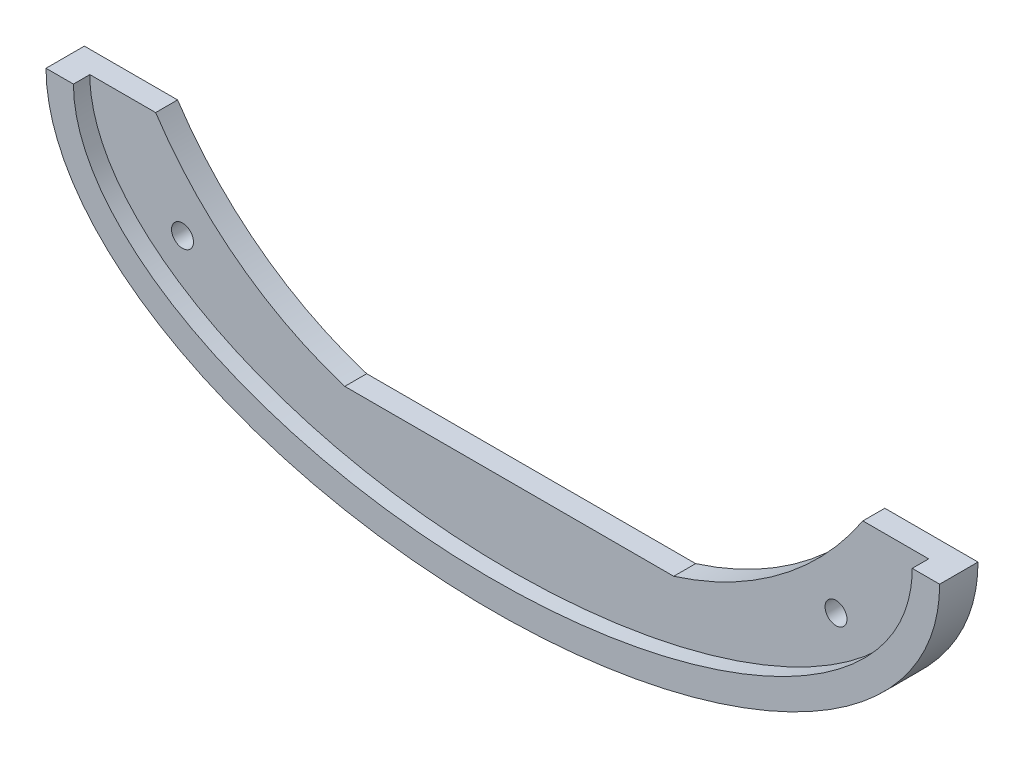
SolidWorks part; units mm, degrees
ref_plane "Alzado" through (0, 0, 0) normal (0, 0, 1) x (1, 0, 0)
ref_plane "Planta" through (0, 0, 0) normal (0, 1, 0) x (1, 0, 0)
ref_plane "Vista lateral" through (0, 0, 0) normal (1, 0, 0) x (0, 0, -1)
sketch "Croquis1" plane through (0, 0, 0) normal (0, 0, 1) x (1, 0, 0)
  line L0 (0, 14) -> (30, 14)
  line L3 (-76.5, 40) -> (-64.5, 40)
  line L5 (0, 14) -> (-30, 14)
  line L6 (0, 0) -> (0, 40) construction
  line L7 (64.5, 40) -> (76.5, 40)
  line L8 (-59.6, 23) -> (59.6, 23) construction
  circle A0 centre (7.25, 8) radius 2
  circle A1 centre (59.6, 23) radius 2
  circle A2 centre (-7.25, 8) radius 2
  circle A3 centre (-59.6, 23) radius 2
  arc A6 (-30, 14) -> (-64.5, 40) centre (-10.6545, 75.5595) cw
  arc A7 (30, 14) -> (64.5, 40) centre (10.6545, 75.5595) ccw
  ellipse E0 centre (0, 40) end of major axis (76.5, 40) minor radius 40 (-76.5, 40) -> (76.5, 40) ccw
  dimension "D3" = 4
  dimension "D5" = 4
  dimension "D10" = 8
  dimension "D2" = 153
  dimension "D4" = 30
  dimension "D6" = 119.2
  dimension "D7" = 15
  dimension "D8" = 40
  dimension "D9" = 12
  dimension "D11" = 14.5
  dimension "D12" = 14
extrude "Saliente-Extruir1" add sketch "Croquis1" along normal blind 4
ref_plane "Plano1" through (0, 0, -3) normal (0, 0, -1) x (-1, 0, 0)
sketch "Croquis2" plane through (0, 0, -3) normal (0, 0, -1) x (-1, 0, 0)
  line L3 (0, 0) -> (0, 33.4572) construction
  line L6 (64.5, 40) -> (76.5, 40) construction
  line L7 (-30, 14) -> (30, 14) construction
  line L8 (-76.5, 40) -> (-64.5, 40) construction
  line L9 (64.5, 40) -> (76.5, 40)
  line L10 (-30, 14) -> (30, 14)
  line L11 (-76.5, 40) -> (-64.5, 40)
  arc A8 (30, 14) -> (64.5, 40) centre (10.6545, 75.5595) ccw construction
  circle A10 centre (-59.6, 23) radius 2 construction
  circle A12 centre (7.25, 8) radius 2 construction
  circle A13 centre (-7.25, 8) radius 2 construction
  arc A14 (-64.5, 40) -> (-30, 14) centre (-10.6545, 75.5595) ccw construction
  arc A15 (30, 14) -> (64.5, 40) centre (10.6545, 75.5595) ccw
  circle A17 centre (-59.6, 23) radius 2
  circle A19 centre (7.25, 8) radius 2
  circle A20 centre (-7.25, 8) radius 2
  arc A21 (-64.5, 40) -> (-30, 14) centre (-10.6545, 75.5595) ccw
  circle A22 centre (59.6, 23) radius 2 construction
  circle A23 centre (59.6, 23) radius 2
  ellipse E0 centre (0, 40) end of major axis (-76.5, 40) minor radius 40 (-76.5, 40) -> (76.5, 40) ccw construction
  ellipse E1 centre (0, 40) end of major axis (-76.5, 40) minor radius 40 (-76.5, 40) -> (76.5, 40) ccw
extrude "Saliente-Extruir2" add sketch "Croquis2" along normal blind 4 separate body
ref_plane "Plano2" through (0, 0, 4) normal (0, 0, 1) x (1, 0, 0)
sketch "Croquis3" plane through (0, 0, 4) normal (0, 0, 1) x (1, 0, 0)
  line L2 (-81.5, 40) -> (-76.5, 40)
  line L3 (81.5, 40) -> (76.5, 40)
  ellipse E1 centre (0, 40) end of major axis (76.5, 40) minor radius 40 (-76.5, 40) -> (76.5, 40) ccw construction
  ellipse E2 centre (0, 40) end of major axis (76.5, 40) minor radius 40 (-76.5, 40) -> (76.5, 40) ccw
  spline S0 degree 1 poles (-81.5, 40) (81.5, 40) knots 0 0 1 1 construction
  spline S1 degree 3 poles (-81.5, 40) (-81.5, 36.7505) (-80.261, 30.281) (-73.3217, 18.4428) (-57.7398, 6.4288) (-31.0655, -2.8514) (0, -6.0743) (31.0655, -2.8514) (57.7398, 6.4288) (73.3217, 18.4428) (80.261, 30.281) (81.5, 36.7505) (81.5, 40) knots 3.141593 3.141593 3.141593 3.141593 3.337942 3.534292 3.926991 4.31969 4.712389 5.105088 5.497787 5.890486 6.086836 6.283185 6.283185 6.283185 6.283185
  dimension "D1" = 5
extrude "Saliente-Extruir3" add sketch "Croquis3" against normal up to surface (11 mm away) contours L3 E2 L2 S1 up to face at (5.25, 8, -7)
sketch "Croquis4" plane through (0, 0, 0) normal (0, 0, 1) x (1, 0, 0)
  line L0 (30, 14) -> (-30, 14) construction
  line L1 (30, 14) -> (-30, 14)
  line L2 (-39.8217, 18) -> (39.8217, 18)
  arc A0 (-64.5, 40) -> (-30, 14) centre (-10.6545, 75.5595) ccw construction
  arc A1 (30, 14) -> (64.5, 40) centre (10.6545, 75.5595) ccw construction
  arc A2 (-39.8217, 18) -> (-30, 14) centre (-10.6545, 75.5595) ccw
  arc A3 (30, 14) -> (39.8217, 18) centre (10.6545, 75.5595) ccw
  dimension "D1" = 4
extrude "Saliente-Extruir4" add sketch "Croquis4" along normal blind 4
sketch "Croquis5" plane through (0, 0, 4) normal (0, 0, 1) x (1, 0, 0)
  line L0 (39.8217, 18) -> (-39.8217, 18) construction
  line L1 (40.755, 18) -> (-40.755, 18)
  line L2 (40.755, 18) -> (40.755, 14)
  line L3 (40.755, 14) -> (-40.755, 14)
  line L4 (-40.755, 18) -> (-40.755, 14)
  point P6 (0, 14)
  dimension "D1" = 4
  dimension "D2" = 81.51
extrude "Saliente-Extruir5" add sketch "Croquis5" along normal blind 45 contours L2 L1 L4 L3
sketch "Croquis6" plane through (0, 14, 0) normal (0, -1, 0) x (-1, 0, 0)
  line L0 (13.075, -29) -> (-13.075, -29) construction
  line L1 (40.755, -4) -> (-40.755, -4) construction
  line L2 (0, -4) -> (0, -39) construction
  line L3 (35.826, -4) -> (35.826, -49) construction
  line L4 (-40.755, -4) -> (40.755, -4) construction
  line L5 (-40.755, -49) -> (40.755, -49) construction
  circle A0 centre (13.075, -29) radius 8.15
  circle A1 centre (-13.075, -29) radius 8.125
  circle A2 centre (35.826, -43.4034) radius 2.65
  circle A3 centre (35.826, -33.4034) radius 2.65
  circle A4 centre (-35.826, -33.4034) radius 2.65
  circle A5 centre (-35.826, -43.4034) radius 2.65
  point P18 (0, -29)
  dimension "D2" = 16.3
  dimension "D3" = 16.25
  dimension "D6" = 5.3
  dimension "D7" = 5.3
  dimension "D4" = 26.15
  dimension "D1" = 25
  dimension "D8" = 10
extrude "Cortar-Extruir1" cut sketch "Croquis6" against normal blind 25 contours A2 | A3 | A0 | A1 | A5 | A4
ref_plane "Plano4" through (0, -1, 0) normal (0, 1, 0) x (1, 0, 0)
sketch "Croquis7" plane through (0, -1, 0) normal (0, 1, 0) x (1, 0, 0)
  line L0 (0, -9.7855) -> (0, 13.9568) construction
  line L1 (-81.5, -4) -> (81.5, -4) construction
  line L2 (-55, -4) -> (-45, -4)
  line L3 (-55, -4) -> (-55, 7)
  line L4 (-55, 7) -> (-45, 7)
  line L5 (-45, -4) -> (-45, 7)
  line L6 (81.5, 7) -> (-81.5, 7) construction
  line L7 (55, 7) -> (45, 7)
  line L8 (55, -4) -> (55, 7)
  line L9 (55, -4) -> (45, -4)
  line L10 (45, -4) -> (45, 7)
  dimension "D1" = 10
  dimension "D2" = 55
extrude "Saliente-Extruir6" [suppressed] add sketch "Croquis7" along normal up to surface and the other way blind 6.08
sketch "Croquis16" [suppressed] plane through (0, -9.08, 0) normal (0, -1, 0) x (1, 0, 0)
  line L8 (-50, -6.5) -> (-50, 4.3) construction
  line L9 (-55, -1.1) -> (-45, -1.1) construction
  line L18 (50, 4.3) -> (50, -6.5) construction
  line L19 (45, -1.1) -> (55, -1.1) construction
  circle A0 centre (-50, -1.1) radius 4
  circle A1 centre (50, -1.1) radius 4
  dimension "D1" = 8
  dimension "D2" = 8
extrude "Cortar-Extruir6" [suppressed] cut sketch "Croquis16" against normal blind 16.3
sketch "Croquis17" plane through (0, 14, 0) normal (0, -1, 0) x (1, 0, 0)
  line L0 (-20.0239, 37.988) -> (-14.3005, 42.0182) construction
  line L1 (-20.5996, 38.8056) -> (-14.8763, 42.8359)
  line L2 (-19.4481, 37.1703) -> (-13.7248, 41.2006)
  line L3 (14.2242, 42.0182) -> (19.9475, 37.988) construction
  line L4 (14.7999, 42.8359) -> (20.5233, 38.8056)
  line L5 (13.6484, 41.2006) -> (19.3718, 37.1703)
  line L7 (-0.0382, 31.8728) -> (-0.0382, 6.8728) construction
  line L8 (-14.3005, 42.0182) -> (14.2242, 42.0182) construction
  line L9 (-20.0239, 37.988) -> (19.9475, 37.988) construction
  arc A0 (-20.5996, 38.8056) -> (-19.4481, 37.1703) centre (-20.0239, 37.988) ccw
  arc A1 (-13.7248, 41.2006) -> (-14.8763, 42.8359) centre (-14.3005, 42.0182) ccw
  arc A2 (14.7999, 42.8359) -> (13.6484, 41.2006) centre (14.2242, 42.0182) ccw
  arc A3 (19.3718, 37.1703) -> (20.5233, 38.8056) centre (19.9475, 37.988) ccw
  arc A4 (-20.8514, 31.4391) -> (-21.2225, 29.203) centre (-13.075, 29) ccw
  arc A6 (-10.8066, 17.5553) -> (11.1701, 17.5553) centre (0.1818, 45.4654) ccw
  arc A7 (-11.1729, 16.6248) -> (11.5364, 16.6248) centre (0.1818, 45.4654) ccw
  arc A8 (-10.8066, 17.5553) -> (-11.1729, 16.6248) centre (-10.9898, 17.09) ccw
  arc A9 (11.5364, 16.6248) -> (11.1701, 17.5553) centre (11.3533, 17.09) ccw
  circle A10 centre (-13.075, 29) radius 8.15 construction
  arc A13 (20.7751, 31.4391) -> (21.1461, 29.203) centre (12.9987, 29) cw
  ellipse E0 centre (-0.0382, 20.6274) end of major axis (3.8018, 20.6274) minor radius 1.3066
  spline S0 degree 2 poles (-20.8514, 31.4391) (-23.6077, 31.2523) (-25.4765, 33.8858) knots 0 0 0 1 1 1
  spline S1 degree 3 poles (-25.4765, 33.8858) (-24.9367, 29.7669) (-23.9591, 29.7982) (-21.2225, 29.203) knots 0 0 0 0 0.707855 0.707855 0.707855 0.707855
  spline S2 degree 3 poles (25.4002, 33.8858) (24.8603, 29.7669) (23.8827, 29.7982) (21.1461, 29.203) knots 0 0 0 0 0.707855 0.707855 0.707855 0.707855
  spline S3 degree 2 poles (20.7751, 31.4391) (23.5313, 31.2523) (25.4002, 33.8858) knots 0 0 0 1 1 1
  point P2 (-17.1622, 40.0031)
  point P7 (17.0859, 40.0031)
  point P54 (-0.0382, 37.988)
  dimension "D2" = 1
  dimension "D1" = 7
extrude "Saliente-Extruir9" add sketch "Croquis17" along normal blind 2
sketch "Croquis18" [suppressed] plane through (0, 0, -6.6) normal (0, 0, -1) x (-1, 0, 0)
  line L0 (0, 12) -> (0, -15.2947) construction
  line L1 (30, 12) -> (-30, 12) construction
  line L2 (50, 2.42) -> (50, -5.58) construction
  line L3 (51.5, 2.42) -> (51.5, -5.58)
  line L4 (48.5, 2.42) -> (48.5, -5.58)
  line L5 (55, -9.08) -> (55, 5.7348) construction
  line L6 (45, -9.08) -> (45, 1.7946) construction
  line L7 (-50, 2.42) -> (-50, -5.58) construction
  line L8 (-51.5, 2.42) -> (-51.5, -5.58)
  line L9 (-48.5, 2.42) -> (-48.5, -5.58)
  line L10 (45, -9.08) -> (55, -9.08) construction
  arc A0 (51.5, 2.42) -> (48.5, 2.42) centre (50, 2.42) ccw
  arc A1 (48.5, -5.58) -> (51.5, -5.58) centre (50, -5.58) ccw
  arc A2 (-51.5, 2.42) -> (-48.5, 2.42) centre (-50, 2.42) cw
  arc A3 (-48.5, -5.58) -> (-51.5, -5.58) centre (-50, -5.58) cw
  point P7 (50, -1.58)
  point P18 (-50, -1.58)
  dimension "D2" = 1.5
  dimension "D1" = 8
  dimension "D3" = 3.5
extrude "Cortar-Extruir7" [suppressed] cut sketch "Croquis18" against normal through all
sketch "Croquis19" [suppressed] plane through (0, 0, -3) normal (0, 0, 1) x (1, 0, 0)
  line L0 (0, 0) -> (0, 34.2296) construction
  line L2 (-64.5, 40) -> (-81.5, 40) construction
  circle A0 centre (0, -2.5) radius 0.75
  circle A1 centre (-79, 36.5) radius 0.75
  circle A2 centre (79, 36.5) radius 0.75
  dimension "D1" = 1.5
  dimension "D2" = 1.5
  dimension "D4" = 2.5
  dimension "D3" = 2.5
  dimension "D5" = 3.5
sketch "Croquis20" plane through (0, 0, 0) normal (1, 0, 0) x (0, 0, -1)
  line L0 (0, 40) -> (0, -5)
  line L1 (-4, -5) -> (7, -5) construction
  line L2 (0, -5) -> (-49.6594, -5)
  line L3 (-49.6594, -5) -> (-49.6594, 40)
  line L4 (-49.6594, 40) -> (0, 40)
extrude "Cortar-Extruir9" cut sketch "Croquis20" against normal through all both and the other way through all
sketch "Croquis21" plane through (0, 0, -7) normal (0, 0, -1) x (-1, 0, 0)
  circle A0 centre (-7.25, 8) radius 2 construction
  circle A1 centre (7.25, 8) radius 2 construction
  circle A2 centre (-7.25, 8) radius 2
  circle A3 centre (7.25, 8) radius 2
extrude "Saliente-Extruir11" add sketch "Croquis21" against normal up to surface (4 mm away) up to face at (0, 23.6757, -3)
extrude "Saliente-Extruir10" [suppressed] add sketch "Croquis19" along normal blind 6
